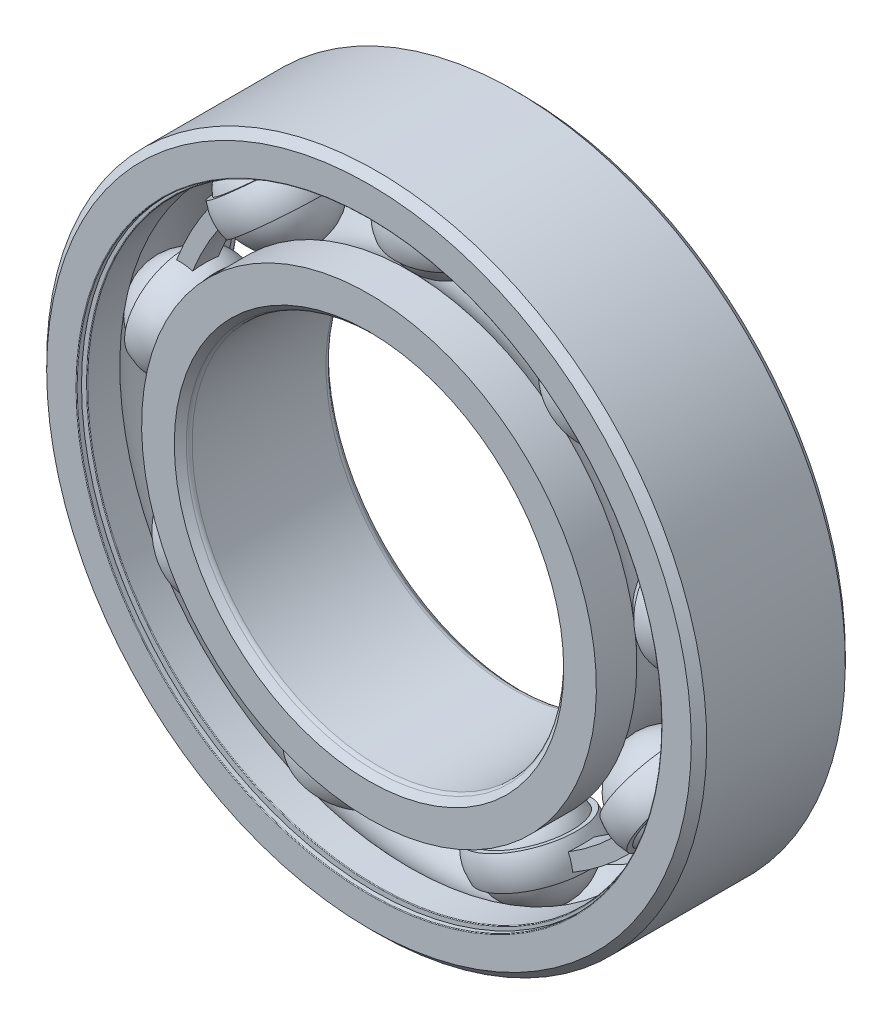
SolidWorks part; units mm, degrees
ref_plane "Front Plane" through (0, 0, 0) normal (0, 0, 1) x (1, 0, 0)
ref_plane "Top Plane" through (0, 0, 0) normal (0, 1, 0) x (1, 0, 0)
ref_plane "Right Plane" through (0, 0, 0) normal (1, 0, 0) x (0, 0, -1)
sketch "Sketch1" plane through (0, 0, 0) normal (0, 0, 1) x (1, 0, 0)
  line L0 (-15, 0) -> (15, 0) construction
  line L1 (-8.5, 0) -> (8.5, 0) construction
  circle A0 centre (0, 0) radius 8.5 construction
  circle A1 centre (0, 0) radius 15 construction
  point P3 (0, 0)
  point P6 (0, 0)
  point P7 (0, -8.5)
  point P11 (0, -15)
  point P12 (0, 8.5)
  point P13 (0, 15)
  dimension "OD" = 30
  dimension "ID" = 17
sketch "Sketch2" plane through (0, 0, 0) normal (1, 0, 0) x (0, 0, -1)
  line L0 (-3.5, 15) -> (3.5, 15) construction
  line L1 (0, 15) -> (0, -15) construction
  line L2 (3.15, 15) -> (-3.15, 15)
  line L3 (-3.15, 15) -> (-3.5, 14.65)
  line L4 (-3.5, 14.65) -> (-3.5, 13.1654)
  line L5 (-3.5, 13.1654) -> (-1.6625, 13.1654)
  line L6 (3.5, 13.1654) -> (1.6625, 13.1654)
  line L7 (3.5, 14.65) -> (3.5, 13.1654)
  line L8 (3.15, 15) -> (3.5, 14.65)
  line L9 (0, 15) -> (0, 11.75) construction
  line L10 (0, 11.75) -> (0, 8.5) construction
  line L11 (0, 15) -> (0, -15) construction
  line L12 (-3.5, 0) -> (3.5, 0) construction
  line L13 (3.5, 8.5) -> (-3.5, 8.5) construction
  line L14 (0, 13.9334) -> (0, 9.5666) construction
  line L15 (-3.5, -8.5) -> (3.5, -8.5) construction
  line L16 (-3.5, -8.5) -> (-3.5, 8.5) construction
  line L17 (3.5, 15) -> (3.5, -15) construction
  arc A0 (-1.6625, 13.1654) -> (1.6625, 13.1654) centre (0, 11.75) cw
  circle A1 centre (0, 11.75) radius 2.1834 construction
  point P14 (0, 8.5)
  point P17 (0, 0)
  point P21 (0, 15)
  point P29 (0, 8.5)
  point P30 (0, -8.5)
  point P35 (0, 13.9334)
  dimension "Approx. Ball Dia." = 4.3668
  dimension "Width" = 7
  dimension "D1" = 45
  dimension "D2" = 0.35
  dimension "D3" = 3.325
  dimension "D4" = 1.4154
  dimension "For Shaft Diameter" = 17
  dimension "For Housing ID" = 30
sketch "Sketch3" plane through (0, 0, 0) normal (1, 0, 0) x (0, 0, -1)
  line L0 (3.15, 15) -> (3.5, 14.65) construction
  line L1 (3.5, 14.65) -> (3.5, 13.1654) construction
  line L2 (3.5, 13.1654) -> (1.6625, 13.1654) construction
  line L3 (-3.5, 13.1654) -> (-1.6625, 13.1654) construction
  line L4 (-3.5, 14.65) -> (-3.5, 13.1654) construction
  line L5 (-3.15, 15) -> (-3.5, 14.65) construction
  line L6 (3.15, 15) -> (-3.15, 15) construction
  line L7 (3.15, 15) -> (3.5, 14.65)
  line L8 (3.5, 14.65) -> (3.5, 13.1654)
  line L9 (3.5, 13.1654) -> (1.6625, 13.1654)
  line L10 (-3.5, 13.1654) -> (-1.6625, 13.1654)
  line L11 (-3.5, 14.65) -> (-3.5, 13.1654)
  line L12 (-3.15, 15) -> (-3.5, 14.65)
  line L13 (3.15, 15) -> (-3.15, 15)
  arc A0 (1.6625, 13.1654) -> (-1.6625, 13.1654) centre (0, 11.75) ccw construction
  arc A1 (1.6625, 13.1654) -> (-1.6625, 13.1654) centre (0, 11.75) ccw
revolve "Revolve1" add sketch "Sketch3" angle 360 about L12
sketch "Sketch8" plane through (0, 0, 0) normal (1, 0, 0) x (0, 0, -1)
  line L0 (-3.5, 13.1654) -> (-1.6625, 13.1654) construction
  line L1 (-3.276, 13.1654) -> (-3.15, 13.1654)
  line L2 (-3.276, 13.1654) -> (-3.276, 13.7769) construction
  line L3 (-3.276, 13.7769) -> (-3.15, 13.7769)
  line L4 (-3.15, 13.1654) -> (-3.15, 13.7769)
  line L5 (3.5, 13.1654) -> (1.6625, 13.1654) construction
  line L6 (3.15, 13.1654) -> (3.276, 13.1654)
  line L7 (3.15, 13.1654) -> (3.15, 13.7769)
  line L8 (3.15, 13.7769) -> (3.276, 13.7769)
  line L9 (3.276, 13.1654) -> (3.276, 13.7769) construction
  line L10 (-3.15, 13.7769) -> (3.15, 13.7769) construction
  line L11 (0, 15) -> (0, -15) construction
  line L12 (-3.276, 13.7769) -> (-3.276, 14.3885) construction
  line L13 (-3.276, 14.3885) -> (-3.276, 15) construction
  line L14 (-3.5, 15) -> (3.5, 15) construction
  line L15 (-3.276, 13.1654) -> (-3.5, 13.1654)
  line L16 (-3.5, 13.1654) -> (-3.5, 13.2914)
  line L17 (-3.5, 14.65) -> (-3.5, 13.1654) construction
  line L18 (-3.5, 13.2914) -> (-3.276, 13.2914)
  line L19 (-3.276, 13.2914) -> (-3.276, 13.7769)
  line L20 (3.276, 13.1654) -> (3.5, 13.1654)
  line L21 (3.5, 13.1654) -> (3.5, 13.2914)
  line L22 (3.5, 14.65) -> (3.5, 13.1654) construction
  line L23 (3.5, 13.2914) -> (3.276, 13.2914)
  line L24 (3.276, 13.2914) -> (3.276, 13.7769)
  point P12 (0, 13.7769)
  dimension "D1" = 6.3
  dimension "D2" = 0.126
revolve "Cut-Revolve1" cut sketch "Sketch8" angle 360 about L12
sketch "Sketch4" plane through (0, 0, 0) normal (1, 0, 0) x (0, 0, -1)
  line L0 (0, 15) -> (0, -15) construction
  line L1 (0, 15) -> (0, -15) construction
  line L2 (-3.15, 8.5) -> (-3.5, 8.85)
  line L3 (-3.5, 8.85) -> (-3.5, 10.3346)
  line L5 (-3.5, 10.3346) -> (-1.6625, 10.3346)
  line L6 (-3.15, 8.5) -> (3.15, 8.5)
  line L8 (3.15, 8.5) -> (3.5, 8.85)
  line L10 (3.5, 8.85) -> (3.5, 10.3346)
  line L11 (3.5, 10.3346) -> (1.6625, 10.3346)
  line L12 (-3.5, 14.65) -> (-3.5, 13.1654) construction
  line L13 (3.15, 15) -> (3.5, 14.65) construction
  line L15 (3.5, -14.65) -> (3.5, 14.65) construction
  line L16 (3.15, 15) -> (3.15, -15) construction
  arc A1 (1.6625, 10.3346) -> (-1.6625, 10.3346) centre (0, 11.75) cw
  circle A2 centre (0, 11.75) radius 2.1834 construction
  point P1 (0, 8.5)
revolve "Revolve2" add sketch "Sketch4" angle 360 about L12
sketch "Sketch5" plane through (0, 0, 0) normal (1, 0, 0) x (0, 0, -1)
  line L0 (-2.1834, 11.75) -> (2.1834, 11.75)
  arc A2 (-2.1834, 11.75) -> (2.1834, 11.75) centre (0, 11.75) cw
  arc A3 (1.6625, 13.1654) -> (-1.6625, 13.1654) centre (0, 11.75) ccw construction
revolve "Revolve3" add sketch "Sketch5" angle 360 about L0
sketch "Sketch6" plane through (0, 0, 0) normal (1, 0, 0) x (0, 0, -1)
  line L0 (-1.6625, 13.1654) -> (-1.6625, 12.4577) construction
  line L1 (-1.6625, 12.4577) -> (-1.6625, 11.75) construction
  line L2 (-1.6625, 11.75) -> (-1.6625, 11.0423) construction
  line L3 (-1.6625, 11.0423) -> (-1.6625, 10.3346) construction
  line L4 (-3.5, 12.4577) -> (-3.2609, 12.4577) construction
  line L5 (-1.6625, 12.4577) -> (-1.6625, 11.0423) construction
  line L7 (-3.2609, 12.4577) -> (-3.0218, 12.4577) construction
  line L8 (-3.0218, 12.4577) -> (-2.7828, 12.4577) construction
  line L10 (0, 15) -> (0, -15) construction
  line L11 (0, 15) -> (0, -15) construction
  line L12 (-3.5, 13.1654) -> (-3.5, 12.4577) construction
  line L13 (-2.3046, 12.4577) -> (-2.0655, 12.4577) construction
  line L14 (-3.5, 14.65) -> (-3.5, -14.65) construction
  line L15 (-3.5, 12.4577) -> (-3.5, 11.75) construction
  line L16 (-3.5, 11.75) -> (-3.5, 11.0423) construction
  line L17 (-3.5, 11.0423) -> (-3.5, 10.3346) construction
  line L18 (-2.7828, 12.4577) -> (-2.5437, 12.4577) construction
  line L19 (-2.5437, 12.4577) -> (-2.3046, 12.4577) construction
  line L20 (-2.0655, 12.4577) -> (-2.3046, 12.4577)
  line L21 (-3.5, 11.0423) -> (-3.2609, 11.0423) construction
  line L22 (-3.2609, 11.0423) -> (-3.0218, 11.0423) construction
  line L23 (-3.0218, 11.0423) -> (-2.7828, 11.0423) construction
  line L24 (-2.7828, 11.0423) -> (-2.5437, 11.0423) construction
  line L25 (-2.5437, 11.0423) -> (-2.3046, 11.0423) construction
  line L26 (-2.3046, 11.0423) -> (-2.0655, 11.0423) construction
  line L27 (-2.0655, 11.0423) -> (-2.3046, 11.0423)
  line L28 (-2.5437, 12.4577) -> (-2.5437, 11.0423) construction
  line L30 (-2.4241, 12.4577) -> (-2.4241, 11.0423) construction
  circle A0 centre (0, 11.75) radius 2.1834 construction
  arc A2 (-2.3046, 11.0423) -> (-2.3046, 12.4577) centre (-0.2696, 11.75) cw
  arc A3 (-2.0655, 12.4577) -> (-2.0655, 11.0423) centre (0, 11.75) ccw
revolve "Revolve4" add sketch "Sketch6" angle 360 about L11
sketch "Sketch7" plane through (0, 0, 0) normal (0, 0, 1) x (1, 0, 0)
  line L0 (-2.1834, 11.75) -> (2.1834, 11.75) construction
  line L1 (0, 9.5666) -> (0, 13.9334) construction
  line L2 (0, 0) -> (4.0187, 11.0414) construction
  line L8 (0, 15) -> (0, -15) construction
  line L9 (7.5528, 9.001) -> (8.0077, 9.5431)
  line L10 (0, 15) -> (0, -15) construction
  line L11 (0, 12.4577) -> (0, 11.75)
  arc A1 (7.5528, 9.001) -> (0, 11.75) centre (0, 0) ccw
  arc A2 (8.0077, 9.5431) -> (0, 12.4577) centre (0, 0) ccw
  dimension "D1" = 40
  dimension "D2" = 4.3668
extrude "Boss-Extrude1" add sketch "Sketch7" along normal mid plane 1.1667
pattern_circular "CirPattern1" count 9 over 360 about axis through (0, 0, 3.5) along (0, 0, -1) of bodies 104 134
pattern_circular "CirPattern2" count 9 over 360 about axis through (0, 0, 3.5) along (0, 0, -1) of "Revolve4", "Boss-Extrude1" reverse direction yes
fillet "Fillet1" radius 0.0315 4 edges at (0, -13.1654, -3.15) (0, -13.2914, -3.5) (0, -13.1654, 3.15) (0, -13.2914, 3.5)
fillet "Fillet2" radius 0.2625 2 edges at (0, -8.5, -3.15) (0, -8.5, 3.15)
ref_plane "Plane1" through (4.0187, 11.0414, 0) normal (0.342, 0.9397, 0) x (0.9397, -0.342, 0)
sketch "Sketch9" plane through (4.0187, 11.0414, 0) normal (0.342, 0.9397, 0) x (0.9397, -0.342, 0)
  line L0 (-1.967, -0.5833) -> (-1.967, -1.75)
  line L1 (-1.967, -1.75) -> (-0.8532, -1.75)
  line L2 (-0.8532, -1.75) -> (0, -1.0341)
  line L3 (0, -1.0341) -> (0.8532, -1.75)
  line L4 (0.8532, -1.75) -> (1.967, -1.75)
  line L5 (1.967, -1.75) -> (1.967, -0.5833)
  line L6 (1.967, -0.5833) -> (-1.967, -0.5833)
  line L7 (0, -0.5833) -> (0, 0) construction
  line L8 (-1.967, -0.5833) -> (-1.967, 0) construction
  dimension "D1" = 1.1667
  dimension "D2" = 0.5833
  dimension "D3" = 40
extrude "Boss-Extrude2" [suppressed] add sketch "Sketch9" along normal blind 1.9105 draft 15 and the other way blind 1.9105 draft 10 separate body draft outward yes other way draft outward yes
fillet "Fillet3" [suppressed] radius 0.35
mirror "Mirror1" [suppressed] about plane through (0, 0, 0) normal (0, 0, 1) of bodies 149
pattern_circular "CirPattern3" [suppressed] count 9 over 360 about axis through (0, 0, 3.5) along (0, 0, -1) of bodies 158 149
equation "\"D2@Sketch2\" = \"Width@Sketch2\" * .05"
equation "\"D3@Sketch2\"=\"Width@Sketch2\" * .475"
equation "\"D4@Sketch2\" =  (  (  ( \"OD@Sketch1\" - \"Width@Sketch2\" )  / 2 )  / 3.25 )  / 2.5"
equation "\"D1@Boss-Extrude1\" = \"Width@Sketch2\" / 6"
equation "\"D1@Sketch8\"=\"Width@Sketch2\"*.9"
equation "\"D2@Sketch8\"=\"D1@Sketch8\"*.02"
equation "\"D1@Fillet1\" = \"D2@Sketch8\" * .25"
equation "\"D1@Fillet2\" = \"D2@Sketch2\" * .75"
equation "\"Approx No of Balls@CirPattern1\" = ( pi * \"OD@Sketch1\" ) * .4 / \"Approx. Ball Dia.@Sketch2\""
equation "\"D1@Sketch7\" = 360 / \"Approx No of Balls@CirPattern1\""
equation "\"D1@CirPattern2\" = \"Approx No of Balls@CirPattern1\""
equation "\"D2@Sketch7\"=\"Approx. Ball Dia.@Sketch2\""
equation "\"D2@Sketch9\" = \"D1@Boss-Extrude1\" * .5"
equation "\"D1@Sketch9\"=\"D2@Sketch9\"*2"
equation "\"D1@Boss-Extrude2\"=\"Approx. Ball Dia.@Sketch2\"*.4375"
equation "\"D2@Boss-Extrude2\"=\"D1@Boss-Extrude2\""
equation "\"D1@CirPattern3\" = \"Approx No of Balls@CirPattern1\""
equation "\"D1@Fillet3\"=\"D1@Sketch9\" * .3"
